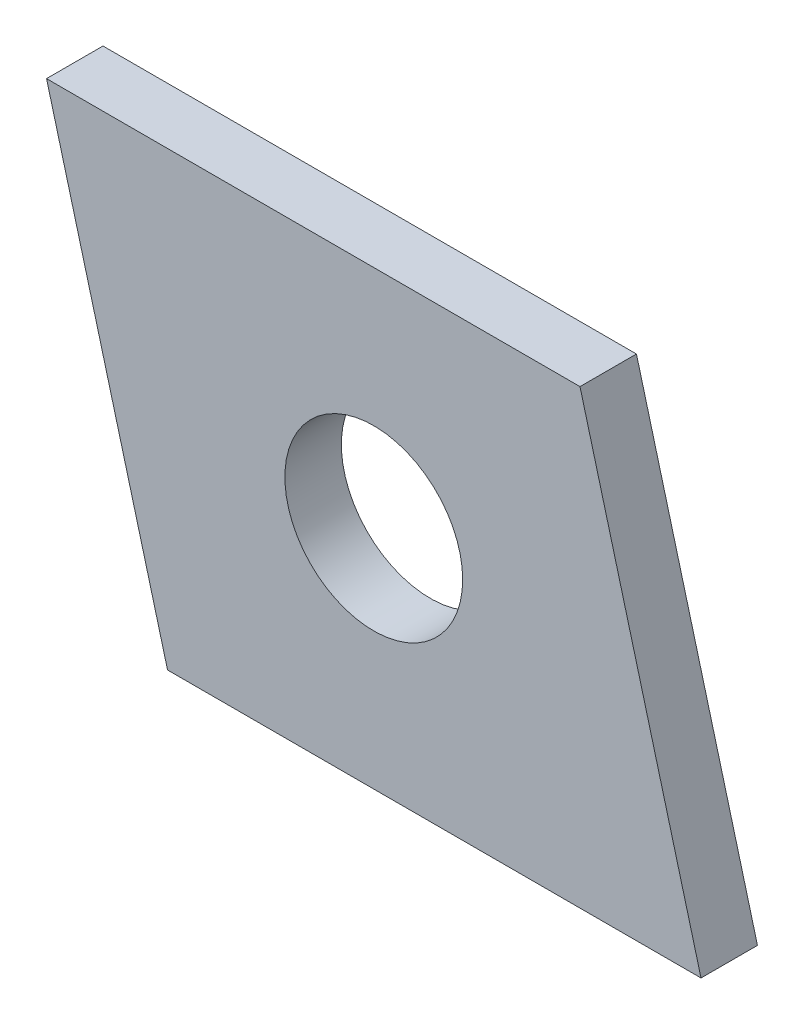
SolidWorks part; units mm, degrees
material "Plain Carbon Steel"
ref_plane "Front Plane" through (0, 0, 0) normal (0, 0, 1) x (1, 0, 0)
ref_plane "Top Plane" through (0, 0, 0) normal (0, 1, 0) x (1, 0, 0)
ref_plane "Right Plane" through (0, 0, 0) normal (1, 0, 0) x (0, 0, -1)
sketch "Sketch1" plane through (0, 0, 0) normal (0, 0, 1) x (1, 0, 0)
  line L0 (-218.7069, 117.1731) -> (-211.901, 91.7731)
  line L1 (-211.901, 91.7731) -> (-181.901, 91.7731)
  line L3 (-188.7069, 117.1731) -> (-218.7069, 117.1731)
  line L8 (-215.304, 104.4731) -> (-185.304, 104.4731) construction
  line L12 (-188.7069, 117.1731) -> (-181.901, 91.7731)
  circle A0 centre (-200.304, 104.4731) radius 5
  point P2 (-200.304, 104.4731)
  dimension "D2" = 10
  dimension "D1" = 25.4
  dimension "D3" = 30
  dimension "D4" = 75
extrude "Boss-Extrude1" add sketch "Sketch1" against normal blind 3.175
